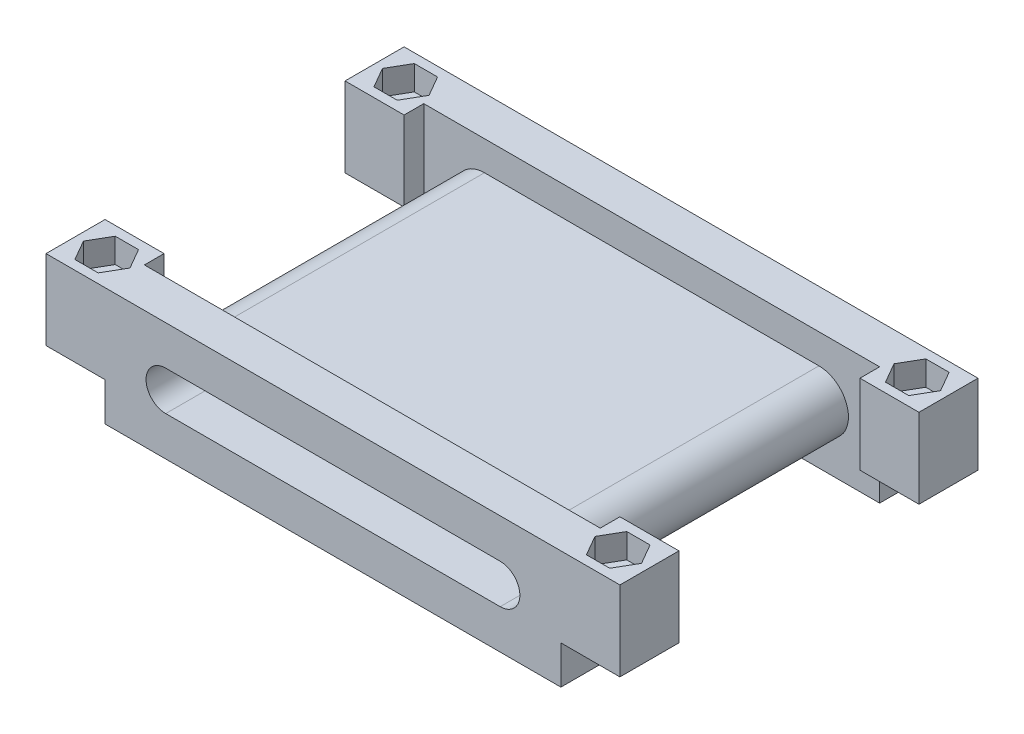
SolidWorks part; units mm, degrees
ref_plane "Plano frontal" through (0, 0, 0) normal (0, 0, 1) x (1, 0, 0)
ref_plane "Plano superior" through (0, 0, 0) normal (0, 1, 0) x (1, 0, 0)
ref_plane "Plano direito" through (0, 0, 0) normal (1, 0, 0) x (0, 0, -1)
sketch "Esboço1" plane through (0, 0, 0) normal (0, 1, 0) x (1, 0, 0)
  line L1 (-29, 3) -> (29, 3)
  line L2 (-29, 3) -> (-29, -3)
  line L3 (-29, -3) -> (29, -3)
  line L4 (29, 3) -> (29, -3)
  line L5 (-29, 3) -> (29, -3) construction
  line L6 (-29, -3) -> (29, 3) construction
  point P0 (0, 0)
  dimension "D1" = 58
  dimension "D2" = 6
extrude "Ressalto-extrusão1" add sketch "Esboço1" along normal blind 8.6
sketch "Esboço2" plane through (0, 0, 0) normal (0, -1, 0) x (1, 0, 0)
  line L0 (-23.95, 3) -> (-23.95, -3)
  line L1 (-29, 3) -> (29, 3) construction
  line L2 (29, -3) -> (-29, -3) construction
  line L3 (23.95, 3) -> (23.95, -3)
  line L4 (-23.95, 3) -> (23.95, 3)
  line L5 (-23.95, 0) -> (23.95, 0) construction
  line L6 (23.95, -3) -> (-23.95, -3)
  dimension "D1" = 47.9
extrude "Ressalto-extrusão2" add sketch "Esboço2" along normal blind 3.4
sketch "Esboço4" plane through (0, 0, 3) normal (0, 0, 1) x (1, 0, 0)
  line L0 (-19, 2.6) -> (19, 2.6) construction
  line L1 (0, 0) -> (0, 2.6) construction
  line L2 (-29, 8.6) -> (29, 8.6) construction
  line L3 (-17, 2.6) -> (17, 2.6) construction
  line L4 (-17, 4.6) -> (17, 4.6)
  line L5 (-17, 0.6) -> (17, 0.6)
  arc A0 (-17, 4.6) -> (-17, 0.6) centre (-17, 2.6) ccw
  arc A1 (17, 0.6) -> (17, 4.6) centre (17, 2.6) ccw
  point P4 (0, 0)
  point P8 (0, 2.6)
  dimension "D1" = 17
  dimension "D2" = 2
  dimension "D3" = 6
extrude "Corte-extrusão2" cut sketch "Esboço4" against normal through all
mirror "Espelhar1" about plane through (-29, 8.6, 3) normal (0, 0, -1) of bodies 104 105
delete or keep bodies "Corpo-Excluir1" type delete bodies bodies 104
sketch "Esboço8" plane through (0, 0, 0) normal (0, -1, 0) x (1, 0, 0)
  line L8 (-23.95, 3) -> (-23.95, 9) construction
  line L9 (-23.95, 9) -> (-29, 9) construction
  line L10 (-29, 9) -> (-29, 3) construction
  line L11 (-29, 3) -> (-23.95, 3) construction
  line L12 (23.95, 9) -> (23.95, 3) construction
  line L13 (23.95, 3) -> (29, 3) construction
  line L14 (29, 3) -> (29, 9) construction
  line L15 (29, 9) -> (23.95, 9) construction
  line L16 (-23.95, 3) -> (-23.95, 9)
  line L17 (-23.95, 9) -> (-29, 9)
  line L18 (-29, 9) -> (-29, 3)
  line L19 (-29, 3) -> (-23.95, 3)
  line L20 (23.95, 9) -> (23.95, 3)
  line L21 (23.95, 3) -> (29, 3)
  line L22 (29, 3) -> (29, 9)
  line L23 (29, 9) -> (23.95, 9)
extrude "Corte-extrusão3" cut sketch "Esboço8" against normal blind 0.5
sketch "Esboço9" plane through (0, 8.6, 0) normal (0, 1, 0) x (1, 0, 0)
  line L0 (-23, -5) -> (-23, -3)
  line L1 (-23, -5) -> (23, -5)
  line L2 (-29, -3) -> (29, -3) construction
  line L3 (-23, -3) -> (23, -3)
  line L4 (23, -5) -> (23, -3)
  line L6 (0, 0) -> (0, -5) construction
  dimension "D1" = 46
  dimension "D3" = 2
extrude "Corte-extrusão4" cut sketch "Esboço9" against normal up to surface (8.1 mm away) up to face at (-26.475, 0.5, 6)
sketch "Esboço10" plane through (0, -3.4, 0) normal (0, -1, 0) x (1, 0, 0)
  line L0 (-23.95, 3) -> (-23.95, 9) construction
  line L1 (23.95, 3) -> (-23.95, 3)
  line L2 (23.95, 3) -> (23.95, 5)
  line L3 (23.95, 5) -> (-23.95, 5)
  line L4 (-23.95, 3) -> (-23.95, 5)
  dimension "D1" = 2
extrude "Corte-extrusão5" cut sketch "Esboço10" against normal up to vertex (3.9 mm away) up to point (-23, 0.5, 5)
sketch "Esboço11" plane through (0, 0.5, 0) normal (0, -1, 0) x (1, 0, 0)
  line L0 (23.95, 9) -> (23.95, 5) construction
  line L1 (23.95, 5) -> (23, 5) construction
  line L2 (-23, 5) -> (-23.95, 5) construction
  line L3 (-23.95, 5) -> (-23.95, 9) construction
  line L4 (23.95, 9) -> (23.95, 5)
  line L5 (23.95, 5) -> (23, 5)
  line L6 (-23, 5) -> (-23.95, 5)
  line L7 (-23.95, 5) -> (-23.95, 9)
  line L8 (-23.95, 9) -> (-23, 9)
  line L9 (-23, 9) -> (-23, 5)
  line L10 (23.95, 9) -> (23, 9)
  line L11 (23, 9) -> (23, 5)
extrude "Corte-extrusão6" cut sketch "Esboço11" along normal through all
sketch "Esboço15" plane through (-23, 0, 0) normal (-1, 0, 0) x (0, 0, 1)
  line L4 (9, 0.5) -> (5, 0.5)
  line L5 (5, 0.5) -> (5, -3.4)
  line L6 (5, -3.4) -> (9, -3.4)
  line L7 (9, -3.4) -> (9, 0.5)
  line L8 (9, 0.5) -> (5, 0.5)
  line L9 (5, 0.5) -> (5, -3.4)
  line L10 (5, -3.4) -> (9, -3.4)
  line L11 (9, -3.4) -> (9, 0.5)
  dimension "D1" = 0
extrude "Ressalto-extrusão4" add sketch "Esboço15" along normal blind 0.17
sketch "Esboço16" plane through (0, 8.6, 0) normal (0, 1, 0) x (1, 0, 0)
  line L0 (-29, -6) -> (29, -6) construction
  line L1 (-29, -9) -> (-29, -3) construction
  line L2 (29, -3) -> (29, -9) construction
  line L3 (26, -3) -> (26, -6) construction
  line L4 (23.6329, -6) -> (24.8164, -8.05)
  line L5 (24.8164, -8.05) -> (27.1836, -8.05)
  line L6 (27.1836, -8.05) -> (28.3671, -6)
  line L7 (28.3671, -6) -> (27.1836, -3.95)
  line L8 (27.1836, -3.95) -> (24.8164, -3.95)
  line L9 (24.8164, -3.95) -> (23.6329, -6)
  line L10 (-28.3671, -6) -> (-27.1836, -8.05)
  line L11 (-27.1836, -8.05) -> (-24.8164, -8.05)
  line L12 (-24.8164, -8.05) -> (-23.6329, -6)
  line L13 (-23.6329, -6) -> (-24.8164, -3.95)
  line L14 (-24.8164, -3.95) -> (-27.1836, -3.95)
  line L15 (-27.1836, -3.95) -> (-28.3671, -6)
  line L16 (23, -3) -> (29, -3) construction
  line L17 (-26, -3) -> (-26, -6) construction
  line L18 (-29, -3) -> (-23, -3) construction
  circle A0 centre (26, -6) radius 2.05 construction
  circle A1 centre (-26, -6) radius 2.05 construction
  circle A2 centre (26, -6) radius 1
  circle A3 centre (-26, -6) radius 1
  dimension "D3" = 2
  dimension "D4" = 2
  dimension "D1" = 4.1
  dimension "D2" = 4.1
extrude "Corte-extrusão9" cut sketch "Esboço16" against normal blind 2.5 contours A2 | L8 L9 L4 L5 L6 L7 A2 | L14 L15 L10 L11 L12 L13 A3 | A3 region at (24.2789, 8.6, 5.0063) region at (-27.7211, 8.6, 5.0063) region at (26, 8.6, 6) region at (-26, 8.6, 6)
extrude "Corte-extrusão10" cut sketch "Esboço16<4>" against normal through all contours A2 | A3 region at (26, 8.6, 6) region at (-26, 8.6, 6)
sketch "Esboço16<4>" plane through (0, 8.6, 0) normal (0, 1, 0) x (1, 0, 0) same geometry as "Esboço16"
sketch "Esboço17" plane through (0, 0, 5) normal (0, 0, -1) x (-1, 0, 0)
  line L2 (-17, 0.6) -> (17, 0.6) construction
  line L3 (17, 4.6) -> (-17, 4.6) construction
  line L4 (17, 5.6) -> (-17, 5.6)
  line L5 (-17, -0.4) -> (17, -0.4)
  line L6 (17, 5.6) -> (-17, 5.6)
  line L7 (-17, -0.4) -> (17, -0.4)
  line L8 (-17, 0.6) -> (17, 0.6)
  line L9 (17, 4.6) -> (-17, 4.6)
  arc A2 (-17, 4.6) -> (-17, 0.6) centre (-17, 2.6) ccw construction
  arc A3 (17, 0.6) -> (17, 4.6) centre (17, 2.6) ccw construction
  arc A4 (17, -0.4) -> (17, 5.6) centre (17, 2.6) ccw
  arc A5 (-17, 5.6) -> (-17, -0.4) centre (-17, 2.6) ccw
  arc A6 (17, -0.4) -> (17, 5.6) centre (17, 2.6) ccw
  arc A7 (-17, 5.6) -> (-17, -0.4) centre (-17, 2.6) ccw
  arc A8 (-17, 4.6) -> (-17, 0.6) centre (-17, 2.6) ccw
  arc A9 (17, 0.6) -> (17, 4.6) centre (17, 2.6) ccw
  dimension "D1" = 1
extrude "Ressalto-extrusão5" add sketch "Esboço17" along normal blind 14.2
sketch "Esboço18" plane through (-23, 0, 0) normal (1, 0, 0) x (0, 0, -1)
  line L4 (-3, 0.5) -> (-3, 8.6)
  line L5 (-3, 8.6) -> (-5, 8.6)
  line L6 (-5, 8.6) -> (-5, 0.5)
  line L7 (-5, 0.5) -> (-3, 0.5)
  line L8 (-3, 0.5) -> (-3, 8.6)
  line L9 (-3, 8.6) -> (-5, 8.6)
  line L10 (-5, 8.6) -> (-5, 0.5)
  line L11 (-5, 0.5) -> (-3, 0.5)
  dimension "D1" = 0
extrude "Corte-extrusão11" cut sketch "Esboço18" against normal blind 0.17
sketch "Esboço19" plane through (23, 0, 0) normal (-1, 0, 0) x (0, 0, 1)
  line L4 (5, 0.5) -> (5, 8.6)
  line L5 (5, 8.6) -> (3, 8.6)
  line L6 (3, 8.6) -> (3, 0.5)
  line L7 (3, 0.5) -> (5, 0.5)
  line L8 (5, 0.5) -> (5, 8.6)
  line L9 (5, 8.6) -> (3, 8.6)
  line L10 (3, 8.6) -> (3, 0.5)
  line L11 (3, 0.5) -> (5, 0.5)
  dimension "D1" = 0
extrude "Corte-extrusão12" cut sketch "Esboço19" against normal blind 0.17
sketch "Esboço20" plane through (23, 0, 0) normal (1, 0, 0) x (0, 0, -1)
  line L4 (-5, 0.5) -> (-9, 0.5)
  line L5 (-9, 0.5) -> (-9, -3.4)
  line L6 (-9, -3.4) -> (-5, -3.4)
  line L7 (-5, -3.4) -> (-5, 0.5)
  line L8 (-5, 0.5) -> (-9, 0.5)
  line L9 (-9, 0.5) -> (-9, -3.4)
  line L10 (-9, -3.4) -> (-5, -3.4)
  line L11 (-5, -3.4) -> (-5, 0.5)
  dimension "D1" = 0
extrude "Ressalto-extrusão6" add sketch "Esboço20" along normal blind 0.17
sketch "Esboço23" plane through (-29, 0, 0) normal (-1, 0, 0) x (0, 0, 1)
  line L4 (3, 0.5) -> (9, 0.5)
  line L5 (9, 0.5) -> (9, 8.6)
  line L6 (9, 8.6) -> (3, 8.6)
  line L7 (3, 8.6) -> (3, 0.5)
  line L8 (3, 0.5) -> (9, 0.5)
  line L9 (9, 0.5) -> (9, 8.6)
  line L10 (9, 8.6) -> (3, 8.6)
  line L11 (3, 8.6) -> (3, 0.5)
  dimension "D1" = 0
extrude "Ressalto-extrusão9" add sketch "Esboço23" along normal blind 0.17
sketch "Esboço24" plane through (29, 0, 0) normal (1, 0, 0) x (0, 0, -1)
  line L4 (-9, 0.5) -> (-3, 0.5)
  line L5 (-3, 0.5) -> (-3, 8.6)
  line L6 (-3, 8.6) -> (-9, 8.6)
  line L7 (-9, 8.6) -> (-9, 0.5)
  line L8 (-9, 0.5) -> (-3, 0.5)
  line L9 (-3, 0.5) -> (-3, 8.6)
  line L10 (-3, 8.6) -> (-9, 8.6)
  line L11 (-9, 8.6) -> (-9, 0.5)
  dimension "D1" = 0
extrude "Ressalto-extrusão10" add sketch "Esboço24" along normal blind 0.17
mirror "Espelhar2" about plane through (-17, 2.6, -9.2) normal (0, 0, -1) of bodies 125 117
